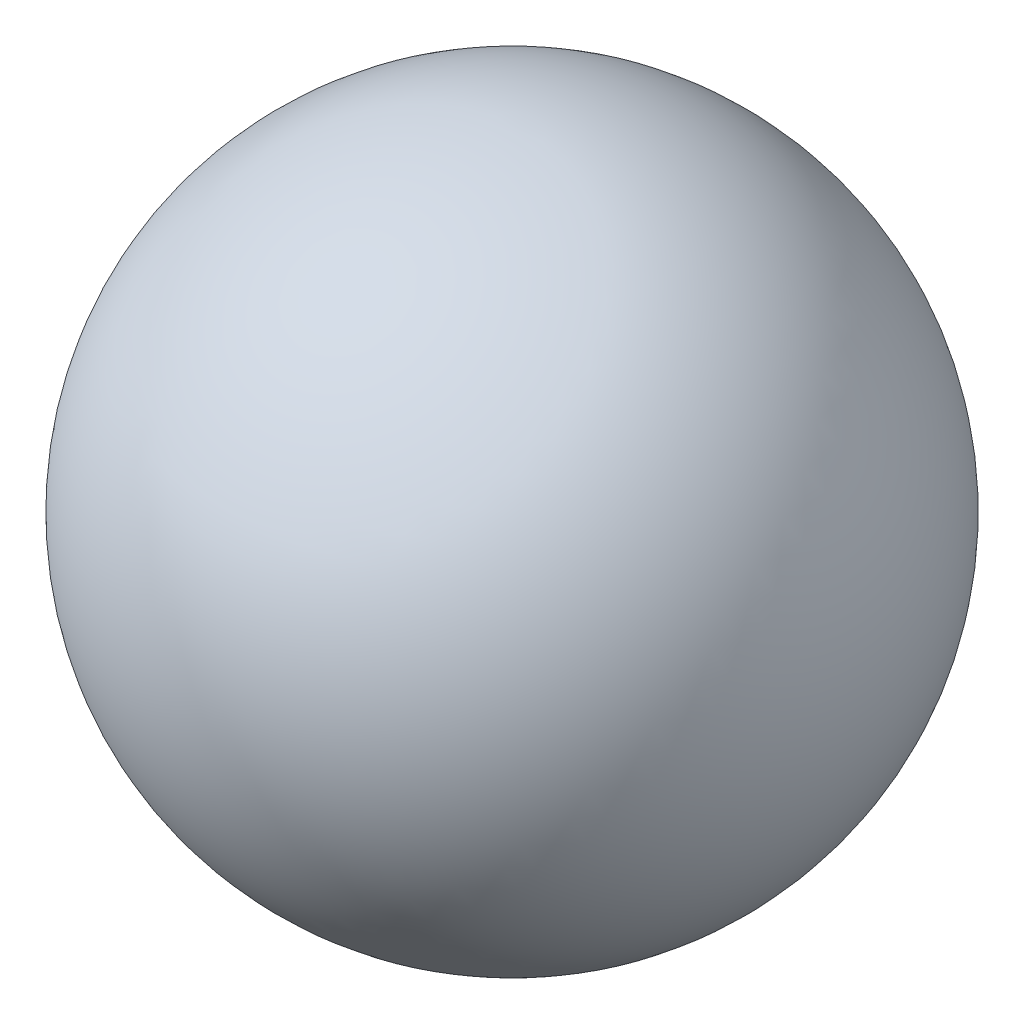
SolidWorks part; units mm, degrees
ref_plane "Front Plane" through (0, 0, 0) normal (0, 0, 1) x (1, 0, 0)
ref_plane "Top Plane" through (0, 0, 0) normal (0, 1, 0) x (1, 0, 0)
ref_plane "Right Plane" through (0, 0, 0) normal (1, 0, 0) x (0, 0, -1)
sketch "Sketch1" plane through (0, 0, 0) normal (0, 0, 1) x (1, 0, 0)
  line L0 (0, 25) -> (0, -25)
  arc A0 (0, -25) -> (0, 25) centre (0, 0) ccw
revolve "Revolve1" add sketch "Sketch1" angle 360 about L0
